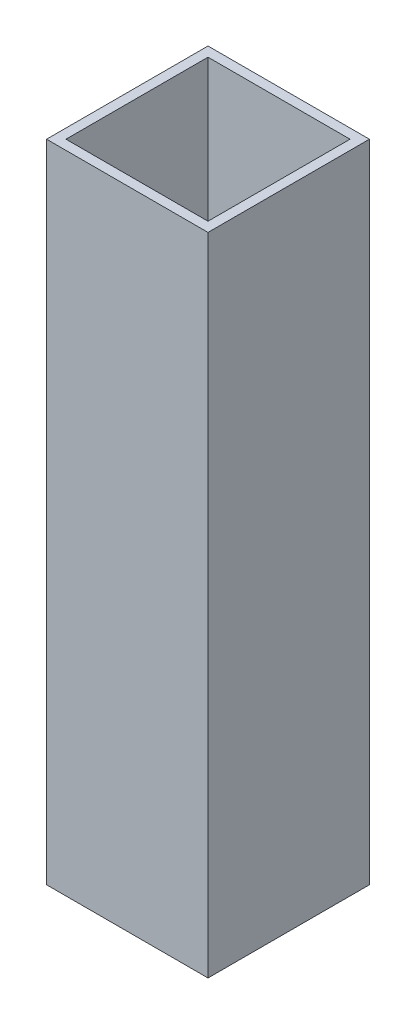
SolidWorks part; units mm, degrees
material "1060 Alloy"
ref_plane "Front Plane" through (0, 0, 0) normal (0, 0, 1) x (1, 0, 0)
ref_plane "Top Plane" through (0, 0, 0) normal (0, 1, 0) x (1, 0, 0)
ref_plane "Right Plane" through (0, 0, 0) normal (1, 0, 0) x (0, 0, -1)
sketch "Sketch3" plane through (0, 0, 0) normal (0, 1, 0) x (1, 0, 0)
  line L0 (0, 86.7063) -> (0, -87.1032) construction
  line L1 (-136.9048, 0) -> (130.9524, 0) construction
  line L7 (-12.5, 12.5) -> (12.5, 12.5)
  line L8 (-12.5, 12.5) -> (-12.5, -12.5)
  line L13 (-12.5, -12.5) -> (12.5, -12.5)
  line L14 (12.5, 12.5) -> (12.5, -12.5)
  line L15 (-12.5, 12.5) -> (12.5, -12.5) construction
  line L16 (-12.5, -12.5) -> (12.5, 12.5) construction
  line L17 (-11, 11) -> (11, 11)
  line L18 (-11, 11) -> (-11, -11)
  line L19 (-11, -11) -> (11, -11)
  line L20 (11, 11) -> (11, -11)
  line L21 (-11, 11) -> (11, -11) construction
  line L22 (-11, -11) -> (11, 11) construction
  point P5 (0, 0)
  point P10 (0, 0)
  dimension "D1" = 25
  dimension "D2" = 25
  dimension "D3" = 22
extrude "Boss-Extrude1" add sketch "Sketch3" along normal blind 50 and the other way blind 50
